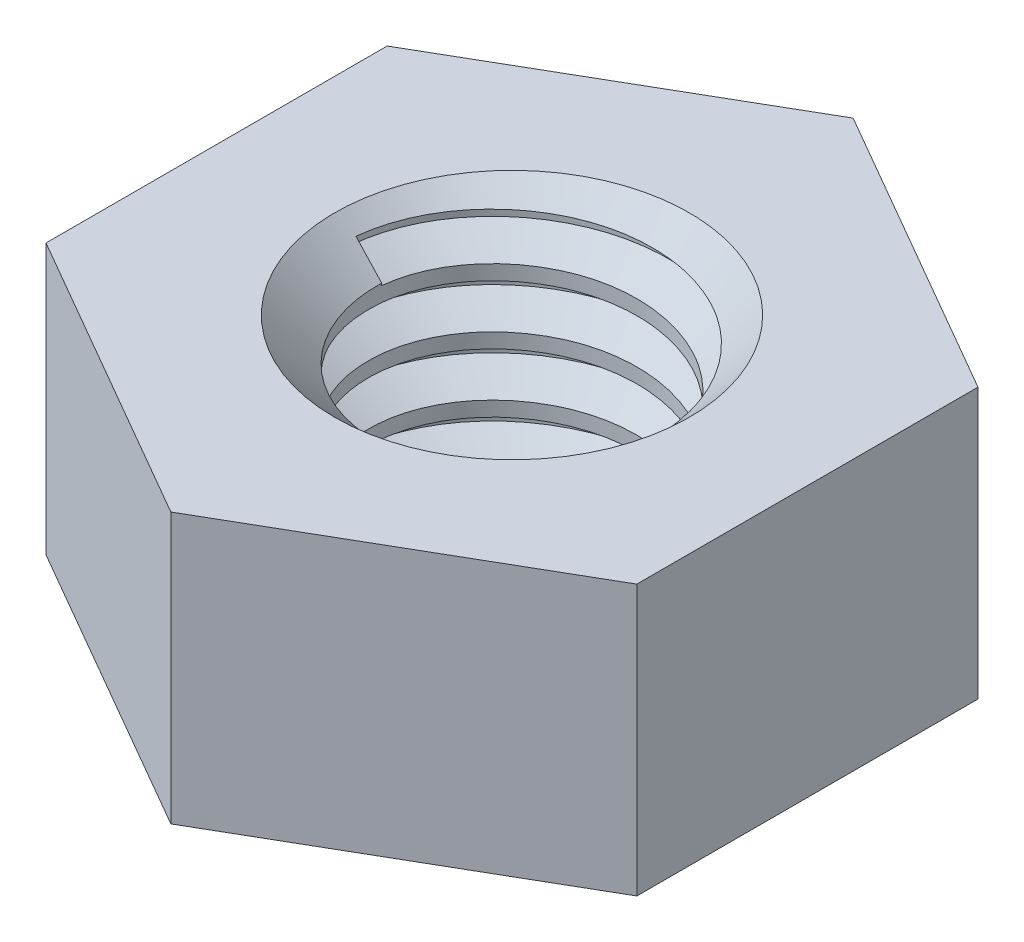
SolidWorks part; units mm, degrees
ref_plane "Front Plane" through (0, 0, 0) normal (0, 0, 1) x (1, 0, 0)
ref_plane "Top Plane" through (0, 0, 0) normal (0, 1, 0) x (1, 0, 0)
ref_plane "Right Plane" through (0, 0, 0) normal (1, 0, 0) x (0, 0, -1)
sketch "Sketch1" plane through (0, 0, 0) normal (0, 1, 0) x (1, 0, 0)
  line L1 (0, 4.0415) -> (-3.5, 2.0207)
  line L2 (-3.5, 2.0207) -> (-3.5, -2.0207)
  line L3 (-3.5, -2.0207) -> (0, -4.0415)
  line L4 (0, -4.0415) -> (3.5, -2.0207)
  line L5 (3.5, -2.0207) -> (3.5, 2.0207)
  line L6 (3.5, 2.0207) -> (0, 4.0415)
  circle A0 centre (0, 0) radius 3.5 construction
  dimension "D1" = 7
extrude "Boss-Extrude1" add sketch "Sketch1" along normal blind 3.2
sketch "Sketch2" plane through (0, 3.2, 0) normal (0, 1, 0) x (1, 0, 0)
  circle A0 centre (0, 0) radius 1.6
  dimension "D1" = 3.2
extrude "Cut-Extrude1" cut sketch "Sketch2" against normal blind 3.2
chamfer "Chamfer1" distance 0.5 angle 45 2 edges at (0, 0, 1.6) (0, 3.2, 1.6)
thread "Thread1" pitch 0.7 method cut profile "Thread Profile1" start angle 2, offset 0.5, length 0, pitch 0.7, diameter 3.2
ref_plane "Plane1" through (-1.599, 3.2, -0.0558) normal (-0.0349, 0, 0.9994) x (-0.9994, 0, -0.0349)
sketch "Thread Profile1" plane through (-1.599, 3.2, -0.0558) normal (-0.0349, 0, 0.9994) x (-0.9994, 0, -0.0349)
  line L0 (0, 0) -> (0, 0.7) construction
  line L1 (0, 0) -> (0.3789, 0.2187)
  line L2 (0.3789, 0.2187) -> (0.3789, 0.3062)
  line L3 (0.3789, 0.3062) -> (0, 0.525)
  line L4 (0.3789, 0.2625) -> (0, 0.2625) construction
  line L11 (0, 0) -> (0, 0.525)
  point P2 (0, 0)
  dimension "Pitch" = 0.7
  dimension "Profile_Angle" = 60
  dimension "Profile_Land" = 0.0875
  dimension "Profile_Height" = 0.3789
